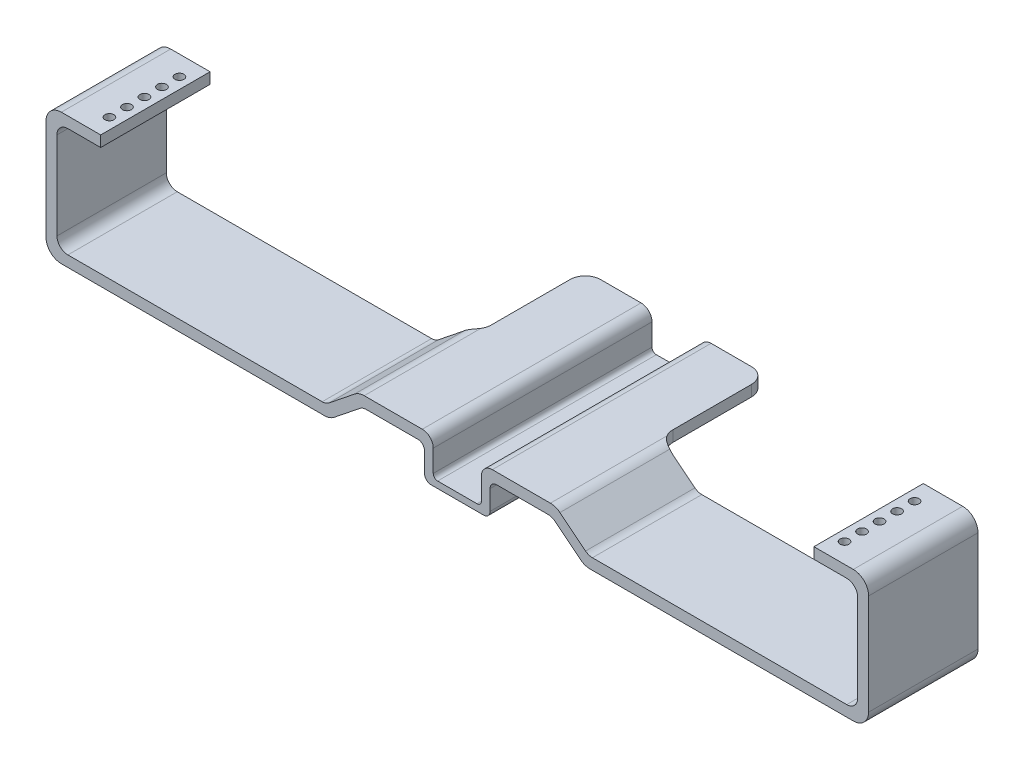
SolidWorks part; units mm, degrees
ref_plane "Front Plane" through (0, 0, 0) normal (0, 0, 1) x (1, 0, 0)
ref_plane "Top Plane" through (0, 0, 0) normal (0, 1, 0) x (1, 0, 0)
ref_plane "Right Plane" through (0, 0, 0) normal (1, 0, 0) x (0, 0, -1)
sketch "Sketch1" plane through (0, 0, 0) normal (0, 1, 0) x (1, 0, 0)
  line L1 (-188, 25) -> (188, 25)
  line L2 (-188, 25) -> (-188, -25)
  line L3 (-188, -25) -> (188, -25)
  line L4 (188, 25) -> (188, -25)
  line L5 (-188, 25) -> (188, -25) construction
  line L6 (-188, -25) -> (188, 25) construction
  point P0 (0, 0)
  dimension "D1" = 376
  dimension "D2" = 50
extrude "Boss-Extrude1" add sketch "Sketch1" along normal blind 5
sketch "Sketch2" plane through (0, 5, 0) normal (0, 1, 0) x (1, 0, 0)
  line L0 (0, 69.6065) -> (0, -68.8567) construction
  line L1 (-188, 25) -> (-183, 25)
  line L2 (188, 25) -> (-188, 25) construction
  line L3 (-183, 25) -> (-183, -25)
  line L4 (-188, -25) -> (188, -25) construction
  line L5 (-183, -25) -> (-188, -25)
  line L6 (-188, -25) -> (-188, 25)
  line L7 (183, -25) -> (188, -25)
  line L8 (183, 25) -> (183, -25)
  line L9 (188, 25) -> (183, 25)
  line L10 (188, -25) -> (188, 25)
  dimension "D1" = 5
extrude "Boss-Extrude2" add sketch "Sketch2" along normal blind 50
fillet "Fillet1" radius 5 2 edges at (183, 5, 0) (-183, 5, 0)
fillet "Fillet2" radius 7 2 edges at (188, 0, 0) (-188, 0, 0)
sketch "Sketch3" plane through (0, 55, 0) normal (0, 1, 0) x (1, 0, 0)
  line L0 (-188, 25) -> (-163, 25)
  line L1 (178, 25) -> (-178, 25) construction
  line L2 (-163, 25) -> (-163, -25)
  line L3 (-178, -25) -> (178, -25) construction
  line L4 (-163, -25) -> (-188, -25)
  line L5 (-188, -25) -> (-188, 25)
  line L6 (0, 67.3571) -> (0, -74.8552) construction
  line L7 (163, -25) -> (188, -25)
  line L8 (163, 25) -> (163, -25)
  line L9 (188, 25) -> (163, 25)
  line L10 (188, -25) -> (188, 25)
  line L11 (-168, 67.3571) -> (-168, -74.8552) construction
  line L12 (-194.1985, 0) -> (212.9435, 0) construction
  circle A0 centre (-168, 0) radius 2.05
  circle A1 centre (-168, 8) radius 2.05
  circle A2 centre (-168, 16) radius 2.05
  circle A3 centre (-168, -8) radius 2.05
  circle A4 centre (-168, -16) radius 2.05
  circle A5 centre (168, -16) radius 2.05
  circle A6 centre (168, -8) radius 2.05
  circle A7 centre (168, 0) radius 2.05
  circle A8 centre (168, 8) radius 2.05
  circle A9 centre (168, 16) radius 2.05
  dimension "D2" = 4.1
  dimension "D3" = 25
  dimension "D6" = 16
  dimension "D7" = 16
  dimension "D1" = 168
  dimension "D4" = 3
  dimension "D5" = 3
extrude "Boss-Extrude3" add sketch "Sketch3" along normal blind 5
fillet "Fillet3" radius 7 2 edges at (188, 60, 0) (-188, 60, 0)
fillet "Fillet4" radius 5 2 edges at (183, 55, 0) (-183, 55, 0)
sketch "Sketch4" plane through (0, 0, 25) normal (0, 0, 1) x (1, 0, 0)
  line L0 (0, 47.1218) -> (0, -52.8517) construction
  line L2 (-178, 5) -> (178, 5) construction
  line L7 (0, 17) -> (-45, 17)
  line L8 (-45, 17) -> (-60, 5)
  line L9 (-60, 5) -> (-60, 0)
  line L10 (-181, 0) -> (181, 0) construction
  line L11 (-60, 0) -> (0, 0)
  line L15 (-5, 12) -> (-43.2461, 12)
  line L16 (-43.2461, 12) -> (-51.9961, 5)
  line L17 (-51.9961, 5) -> (-51.9961, 5)
  line L18 (-51.9961, 5) -> (-5, 5)
  line L19 (60, 0) -> (0, 0)
  line L20 (60, 5) -> (60, 0)
  line L21 (45, 17) -> (60, 5)
  line L22 (0, 17) -> (45, 17)
  line L23 (-5, 12) -> (5, 12)
  line L24 (0, 0) -> (0, 17) construction
  line L25 (-5, 5) -> (-5, 12) construction
  line L26 (-5, 5) -> (5, 5)
  line L27 (51.9961, 5) -> (5, 5)
  line L28 (43.2461, 12) -> (51.9961, 5)
  line L29 (5, 12) -> (43.2461, 12)
  point P12 (0, 0)
  point P13 (0, 12)
  point P25 (0, 5)
  dimension "D1" = 12
  dimension "D2" = 45
  dimension "D3" = 60
  dimension "D4" = 5
extrude "Boss-Extrude4" add sketch "Sketch4" against normal blind 50
sketch "Sketch5" plane through (0, 0, 25) normal (0, 0, 1) x (1, 0, 0)
  line L0 (-51.9961, 5) -> (-58.2461, 0)
  line L1 (-181, 0) -> (181, 0) construction
  line L2 (-58.2461, 0) -> (58.2461, 0)
  line L3 (58.2461, 0) -> (51.9961, 5)
  line L4 (51.9961, 5) -> (-51.9961, 5)
  line L5 (-43.2461, 12) -> (-51.9961, 5) construction
  line L6 (51.9961, 5) -> (43.2461, 12) construction
extrude "Cut-Extrude2" cut sketch "Sketch5" against normal blind 50
fillet "Fillet5" radius 5 4 edges at (60, 5, 0) (-60, 5, 0) (-43.2461, 12, 0) (43.2461, 12, 0)
fillet "Fillet6" radius 7 4 edges at (58.2461, 0, 0) (-58.2461, 0, 0) (-45, 17, 0) (45, 17, 0)
sketch "Sketch6" plane through (0, 0, -25) normal (0, 0, -1) x (-1, 0, 0)
  line L0 (-41.4922, 12) -> (-41.4922, 17)
  line L1 (-42.5445, 17) -> (42.5445, 17) construction
  line L2 (-41.4922, 17) -> (41.4922, 17)
  line L3 (41.4922, 17) -> (41.4922, 12)
  line L4 (41.4922, 12) -> (-41.4922, 12)
extrude "Boss-Extrude5" add sketch "Sketch6" along normal blind 50
fillet "Fillet7" radius 7 4 edges at (-41.4922, 14.5, -25) (41.4922, 14.5, -25) (41.4922, 14.5, -75) (-41.4922, 14.5, -75)
sketch "Sketch8" plane through (0, 0, 25) normal (0, 0, 1) x (1, 0, 0)
  line L0 (0, 43.4437) -> (0, -38.7845) construction
  line L1 (15, 12) -> (-15, 12)
  line L2 (41.4922, 12) -> (-41.4922, 12) construction
  line L3 (-15, 12) -> (-15, -3)
  line L4 (-15, -3) -> (15, -3)
  line L5 (15, 12) -> (15, -3)
  point P10 (0, -3)
  point P11 (0, 12)
  dimension "D1" = 15
  dimension "D2" = 15
extrude "Boss-Extrude6" add sketch "Sketch8" against normal blind 100
fillet "Fillet8" radius 3 4 edges at (-15, 12, -25) (-15, -3, -25) (15, -3, -25) (15, 12, -25)
sketch "Sketch9" plane through (0, 0, 25) normal (0, 0, 1) x (1, 0, 0)
  line L0 (0, 24.6193) -> (0, -15.7136) construction
  line L1 (0, 17) -> (-11, 17)
  line L2 (42.5445, 17) -> (-42.5445, 17) construction
  line L3 (-11, 17) -> (-11, 2)
  line L4 (-9, 0) -> (9, 0)
  line L5 (11, 2) -> (11, 17)
  line L6 (11, 17) -> (0, 17)
  line L8 (15, 0) -> (15, 9) construction
  line L9 (-15, 9) -> (-15, 0) construction
  arc A0 (9, 0) -> (11, 2) centre (9, 2) ccw
  arc A1 (-11, 2) -> (-9, 0) centre (-9, 2) ccw
  dimension "D3" = 2
  dimension "D1" = 4
  dimension "D2" = 4
extrude "Cut-Extrude3" cut sketch "Sketch9" against normal through all
fillet "Fillet9" radius 5 2 edges at (11, 17, -25) (-11, 17, -25)
